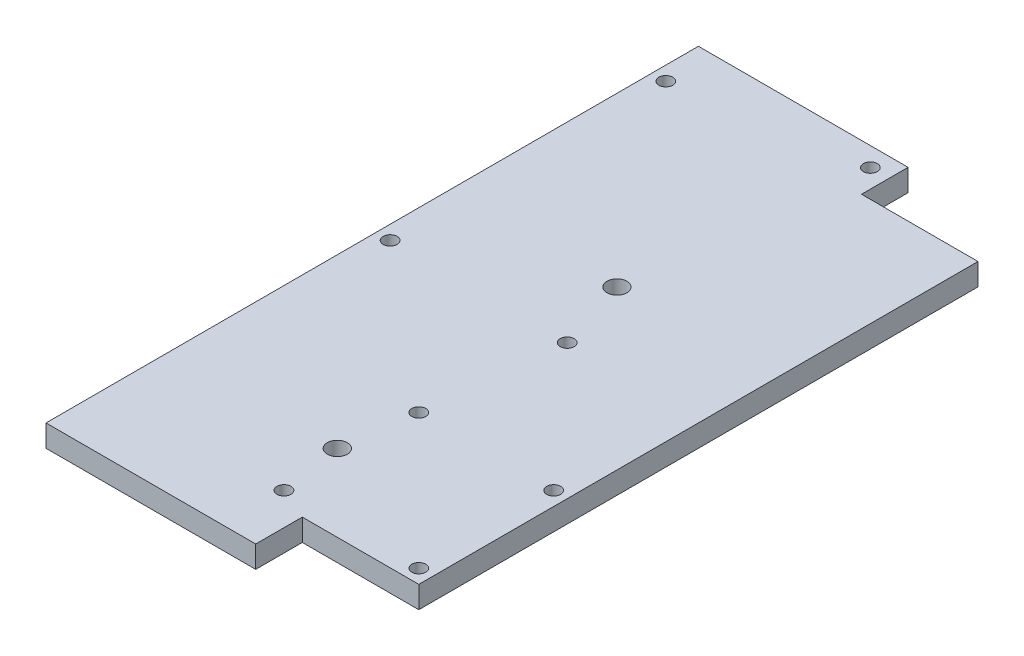
SolidWorks part; units mm, degrees
ref_plane "Front Plane" through (0, 0, 0) normal (0, 0, 1) x (1, 0, 0)
ref_plane "Top Plane" through (0, 0, 0) normal (0, 1, 0) x (1, 0, 0)
ref_plane "Right Plane" through (0, 0, 0) normal (1, 0, 0) x (0, 0, -1)
sketch "Sketch2" plane through (0, 0, 0) normal (0, 1, 0) x (1, 0, 0)
  line L0 (57.15, 177.8) -> (88.9, 177.8) construction
  line L1 (0, 0) -> (57.15, 0)
  line L2 (0, 0) -> (0, 177.8)
  line L3 (0, 177.8) -> (57.15, 177.8)
  line L4 (88.9, 12.7) -> (88.9, 165.1)
  line L5 (88.9, 177.8) -> (57.15, 177.8) construction
  line L6 (88.9, 177.8) -> (88.9, 165.1) construction
  line L7 (88.9, 165.1) -> (57.15, 165.1)
  line L8 (57.15, 177.8) -> (57.15, 165.1)
  line L9 (88.9, 165.1) -> (88.9, 177.8) construction
  line L10 (-1000, 88.9) -> (49000, 88.9) construction
  line L11 (57.15, 0) -> (57.15, 12.7)
  line L12 (88.9, 12.7) -> (57.15, 12.7)
  line L13 (57.15, 0) -> (88.9, 0) construction
  line L14 (88.9, 0) -> (88.9, 12.7) construction
  point P11 (0, 88.9)
  dimension "D1" = 177.8
  dimension "D2" = 88.9
  dimension "D3" = 31.75
  dimension "D4" = 12.7
extrude "Boss-Extrude1" add sketch "Sketch2" along normal blind 5.9944 contours L3 L8 L7 L4 L12 L11 L1 L2
sketch "Sketch3" plane through (0, 5.9944, 0) normal (0, 1, 0) x (1, 0, 0)
  line L0 (0, 0) -> (0, 177.8) construction
  line L1 (88.9, 12.7) -> (57.15, 12.7) construction
  line L2 (0, 177.8) -> (57.15, 177.8) construction
  line L3 (85.09, 53.2638) -> (48.3362, 53.2638) construction
  line L4 (85.09, 53.2638) -> (85.09, 16.51) construction
  line L5 (85.09, 16.51) -> (48.3362, 16.51) construction
  line L6 (48.3362, 53.2638) -> (48.3362, 16.51) construction
  line L7 (88.9, 12.7) -> (88.9, 165.1) construction
  line L8 (0, 0) -> (57.15, 0) construction
  circle A5 centre (52.07, 172.593) radius 1.905
  circle A6 centre (3.81, 165.1) radius 1.905
  circle A7 centre (3.81, 89.9668) radius 1.905
  circle A8 centre (52.07, 89.9668) radius 1.905
  circle A9 centre (48.3362, 53.2638) radius 1.905
  circle A10 centre (85.09, 53.2638) radius 1.905
  circle A11 centre (48.3362, 16.51) radius 1.905
  circle A12 centre (85.09, 16.51) radius 1.905
  point P0 (52.07, 172.593)
  point P1 (3.81, 165.1)
  point P2 (3.81, 89.9668)
  point P3 (52.07, 89.9668)
  point P21 (85.09, 53.2638)
  point P22 (85.09, 16.51)
  point P23 (48.3362, 53.2638)
  point P24 (48.3362, 16.51)
  dimension "D4" = 3.81
  dimension "D5" = 3.81
  dimension "D6" = 3.81
  dimension "D7" = 3.81
  dimension "D9" = 3.81
  dimension "D16" = 3.81
  dimension "D17" = 3.81
  dimension "D18" = 3.81
  dimension "D19" = 3.81
  dimension "D1" = 48.26
  dimension "D2" = 82.6262
  dimension "D3" = 75.1332
  dimension "D8" = 12.7
  dimension "D10" = 36.7538
  dimension "D11" = 36.7538
  dimension "D12" = 3.81
  dimension "D13" = 3.81
  dimension "D14" = 48.3362
  dimension "D15" = 16.51
extrude "Cut-Extrude1" cut sketch "Sketch3" against normal through all both and the other way through all contours A6 | A5 | A8 | A7 | A11 | A9 | A10 | A12
sketch "Sketch4" plane through (0, 5.9944, 0) normal (0, 1, 0) x (1, 0, 0)
  line L0 (0, 0) -> (0, 177.8) construction
  line L1 (0, 0) -> (57.15, 0) construction
  circle A0 centre (45.72, 109.8713) radius 2.7305
  circle A1 centre (45.72, 33.6713) radius 2.7305
  point P4 (0, 0)
  point P6 (10.0676, 80.1857)
  point P8 (0, 0)
  point P9 (45.72, 114.0975)
  point P10 (45.72, 33.6713)
  dimension "D3" = 5.461
  dimension "D4" = 5.461
  dimension "D1" = 76.2
  dimension "D2" = 45.72
  dimension "D5" = 33.6713
extrude "Cut-Extrude2" cut sketch "Sketch4" against normal through all both
equation "\"threaded_insert_hole\"=0.1472"
equation "\"th\"=1.25249"
